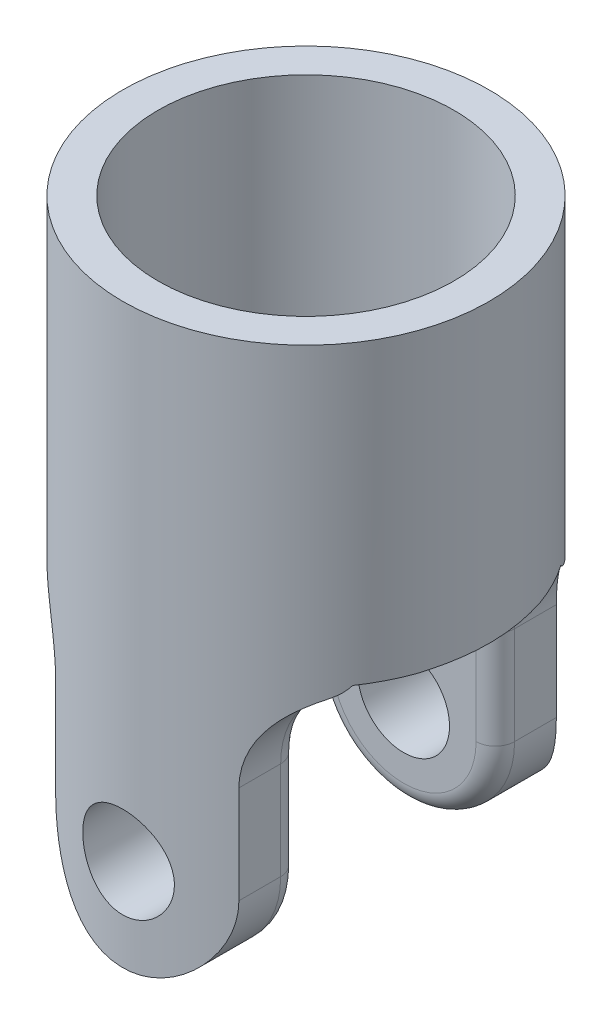
SolidWorks part; units mm, degrees
note: '?' marks a value the reader was unsure of.
ref_plane "Front" through (0, 0, 0) normal (0, 0, 1) x (1, 0, 0)
ref_plane "Top" through (0, 0, 0) normal (0, 1, 0) x (-1, 0, 0)
ref_plane "Right" through (0, 0, 0) normal (1, 0, 0) x (0, 0, -1)
sketch "Sketch1" plane through (0, 0, 0) normal (0, 1, 0) x (-1, 0, 0)
  circle A0 centre (0, 0) radius 19.05
  dimension "D1" = 38.1
extrude "Base-Extrude" add sketch "Sketch1" along normal blind 60
sketch "Sketch2" plane through (0, 0, 0) normal (0, 0, 1) x (1, 0, 0)
  line L0 (0, 0) -> (0, 23.7435) construction
  line L1 (9.525, 9.525) -> (9.525, 19.685)
  line L2 (-9.525, 9.525) -> (-9.525, 19.685)
  line L3 (19.05, 29.21) -> (19.05, -1.3662)
  line L4 (19.05, -1.3662) -> (-19.05, -1.3662)
  line L5 (-19.05, -1.3662) -> (-19.05, 29.21)
  line L6 (19.05, 0) -> (-19.05, 0) construction
  arc A0 (-9.525, 9.525) -> (9.525, 9.525) centre (0, 9.525) ccw
  arc A1 (9.525, 19.685) -> (19.05, 29.21) centre (19.05, 19.685) cw
  arc A2 (-9.525, 19.685) -> (-19.05, 29.21) centre (-19.05, 19.685) ccw
  dimension "D3" = 9.525
  dimension "D1" = 38.1
  dimension "D2" = 19.05
  dimension "D4" = 29.21
extrude "Cut-Extrude1" cut sketch "Sketch2" against normal through all and the other way through all
sketch "Sketch8" plane through (0, 0, 0) normal (1, 0, 0) x (0, 0, -1)
  line L0 (-10.16, -7.4553) -> (10.16, -7.4553)
  line L1 (-10.16, -7.4553) -> (-10.16, 29.1452)
  line L2 (10.16, 29.1452) -> (-10.16, 29.1452)
  line L3 (10.16, 29.1452) -> (10.16, -7.4553)
  point P4 (0, 0)
  dimension "D1" = 10.16
  dimension "D2" = 20.32
extrude "Cut-Extrude5" cut sketch "Sketch8" against normal through all and the other way blind 47.625
sketch "Sketch11" plane through (0, 0, 0) normal (0, 0, 1) x (1, 0, 0)
  circle A0 centre (0, 9.525) radius 4.7625
  dimension "D1" = 9.525
extrude "Cut-Extrude6" cut sketch "Sketch11" against normal through all and the other way through all
ref_axis "Axis1" through (0, 102.9275, -0.0001) along (0, -1, 0)?
fillet "Fillet6" radius 2 10 edges at (11.3465, 25.287, 10.16) (9.525, 14.605, 10.16) (0, 0, 10.16) (-9.525, 14.605, 10.16) (11.3465, 25.287, -10.16) (9.525, 14.605, -10.16) (0, 0, -10.16) (-9.525, 14.605, -10.16) (-11.3465, 25.287, 10.16) (-11.3465, 25.287, -10.16)
scale "Scale1" scale about centroid uniform scaling yes scale factor 0.65
sketch "Sketch12" plane through (0, 52.9275, 0) normal (0, 1, 0) x (1, 0, 0)
  circle A0 centre (0, 0) radius 10
  dimension "D1" = 20
extrude "Cut-Extrude7" cut sketch "Sketch12" against normal blind 15
